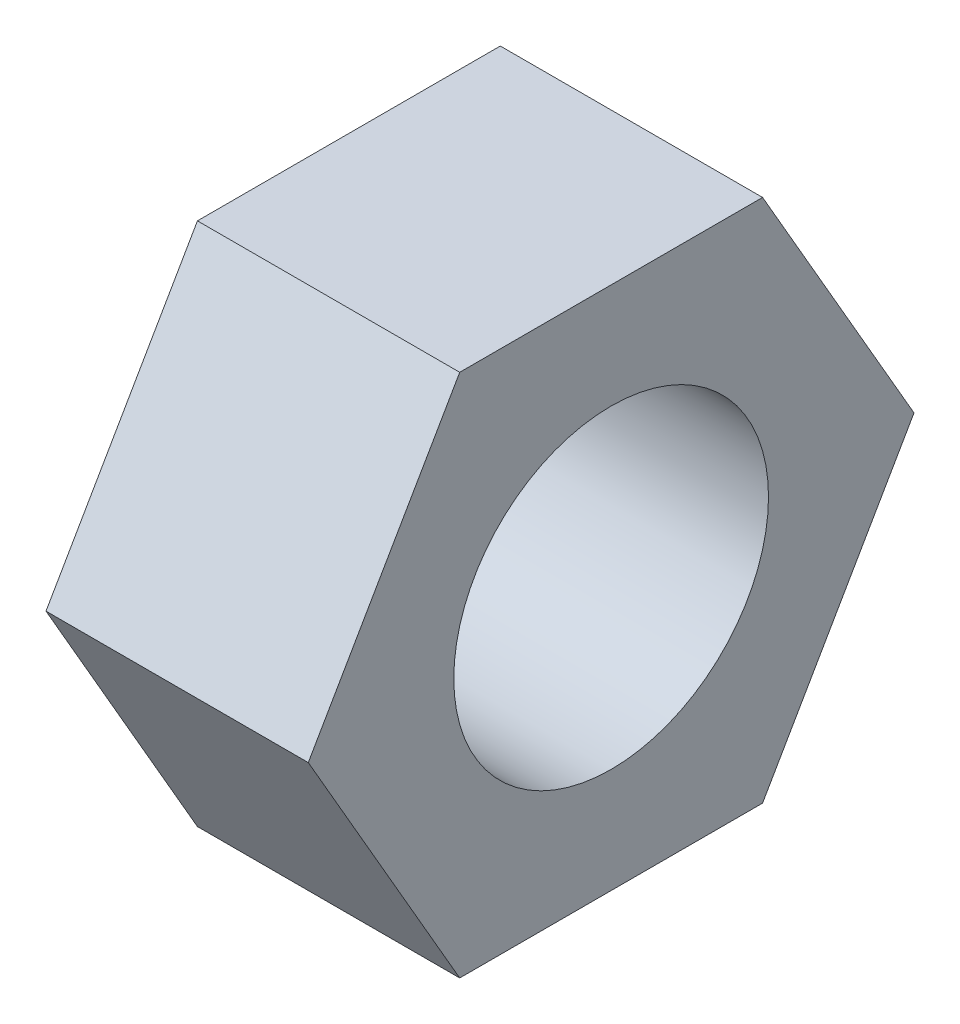
SolidWorks part; units mm, degrees
ref_plane "Front Plane" through (0, 0, 0) normal (0, 0, 1) x (1, 0, 0)
ref_plane "Top Plane" through (0, 0, 0) normal (0, 1, 0) x (1, 0, 0)
ref_plane "Right Plane" through (0, 0, 0) normal (1, 0, 0) x (0, 0, -1)
sketch "Nut Sketch" plane through (0, 0, 0) normal (1, 0, 0) x (0, 0, -1)
  line L0 (5.7735, 0) -> (2.8868, 5)
  line L1 (2.8868, 5) -> (-2.8868, 5)
  line L2 (-2.8868, 5) -> (-5.7735, 0)
  line L3 (-5.7735, 0) -> (-2.8868, -5)
  line L4 (-2.8868, -5) -> (2.8868, -5)
  line L5 (2.8868, -5) -> (5.7735, 0)
extrude "Nut" add sketch "Nut Sketch" along normal blind 5
ref_axis "Engine Axis" through (5.25, 0, 0) along (-1, 0, 0)
sketch "Thread Sketch" plane through (0, 0, 0) normal (0, 0, 1) x (1, 0, 0)
  line L0 (-1000, 0) -> (1000, 0) construction
  line L1 (-1, 0) -> (6, 0)
  line L2 (6, 0) -> (6, 3)
  line L3 (6, 3) -> (-1, 3)
  line L4 (-1, 3) -> (-1, 0)
revolve "Thread" cut sketch "Thread Sketch" angle 360 about L0
